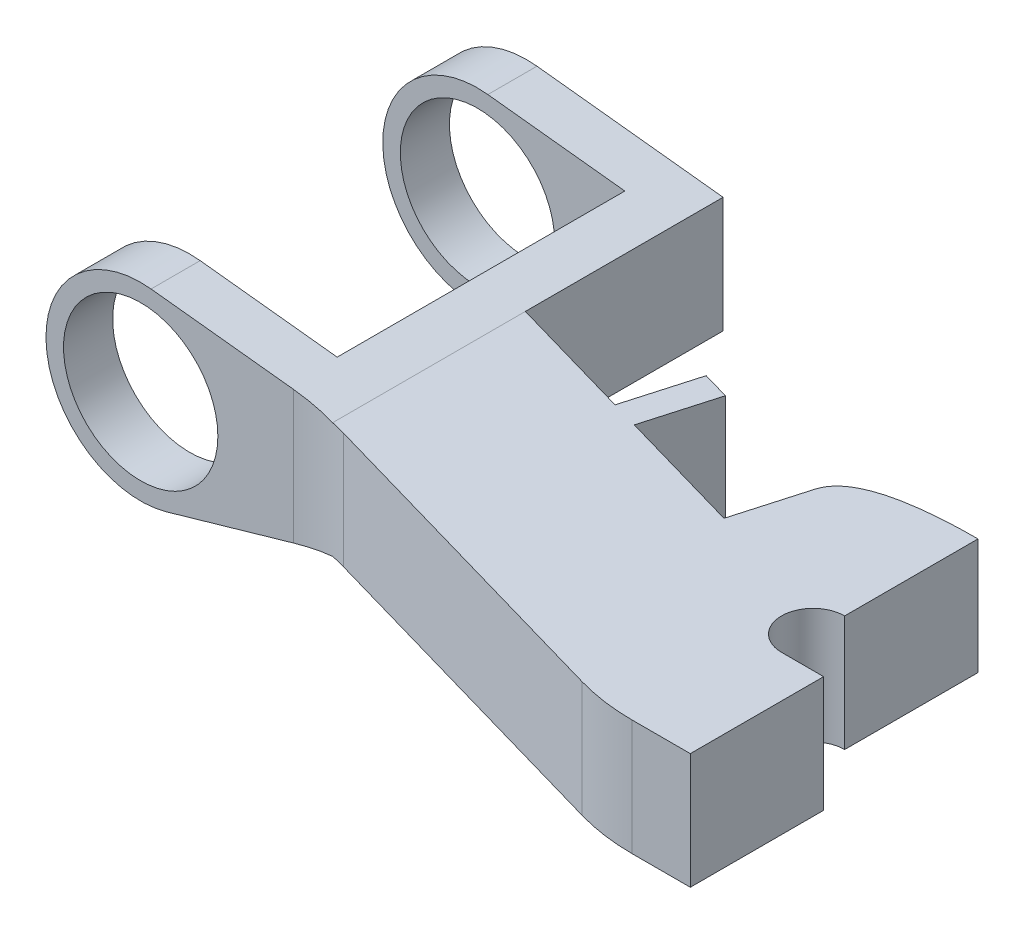
SolidWorks part; units mm, degrees
ref_plane "Спереди" through (0, 0, 0) normal (0, 0, 1) x (1, 0, 0)
ref_plane "Сверху" through (0, 0, 0) normal (0, 1, 0) x (1, 0, 0)
ref_plane "Справа" through (0, 0, 0) normal (1, 0, 0) x (0, 0, -1)
sketch "Эскиз8" plane through (0, 0, 0) normal (0, 1, 0) x (1, 0, 0)
  line L0 (-31.6673, 77.5) -> (-62.0836, 77.5) construction
  line L1 (-85, 43.6529) -> (-6, 21) construction
  line L2 (-106, 13.5) -> (-92.5, 13.5)
  line L3 (-92.5, 13.5) -> (-92.5, 6.5)
  line L4 (-92.5, 6.5) -> (-119.5, 6.5)
  line L6 (-119.5, 6.5) -> (-119.5, 13.5)
  line L7 (-119.5, 13.5) -> (-106, 13.5)
  line L8 (-117, 28.0456) -> (-95, 28.0456) construction
  line L31 (-92.5, 61.5) -> (-119.5, 61.5)
  line L32 (-119.5, 61.5) -> (-119.5, 54.5)
  line L33 (-119.5, 54.5) -> (-92.5, 54.5)
  line L34 (-92.5, 54.5) -> (-92.5, 61.5)
  line L37 (-62.0836, 77.5) -> (-62.0836, 61.5) construction
  line L38 (-62.0836, 61.5) -> (-92.5, 61.5) construction
  line L39 (-11.6673, -9.5) -> (-52.0836, -9.5) construction
  line L44 (-52.0836, -9.5) -> (-52.0836, 6.5) construction
  line L45 (-42.6378, 23.1833) -> (-38.3121, 21.943)
  line L46 (-17.6673, 16.0231) -> (-17.6673, 18.5) construction
  line L47 (-52.0836, 6.5) -> (-92.5, 6.5) construction
  line L48 (-106, 28.0456) -> (-85, 28.0456) construction
  line L52 (-92.5, 54.5) -> (-85, 54.5)
  line L53 (-85, 54.5) -> (-85, 13.5)
  line L54 (-85, 13.5) -> (-92.5, 13.5)
  line L56 (-6, 21) -> (-6, 28) construction
  line L59 (-78, 61.5) -> (-78, 63.0226)
  line L60 (-35.418, 32.0362) -> (-39.7436, 33.2766)
  line L61 (-78, 61.5) -> (-78, 33.3233)
  line L64 (-11.6673, 9.5) -> (-17.6673, 9.5)
  line L65 (-17.6673, 37.5) -> (-17.6673, 18.5) construction
  line L67 (-38.3121, 21.943) -> (-35.418, 32.0362)
  line L68 (-41.1218, 28.4703) -> (-42.6378, 23.1833) construction
  line L69 (-60.3189, 28.2533) -> (-57.4247, 38.3465) construction
  line L70 (-39.7436, 33.2766) -> (-41.1218, 28.4703)
  line L71 (-41.1218, 28.4703) -> (-36.7961, 27.2299)
  line L72 (-42.6378, 23.1833) -> (-78, 33.3233)
  line L79 (-38.3121, 21.943) -> (-17.6673, 16.0231) construction
  line L82 (-35.418, 32.0362) -> (-33.8512, 37.5) construction
  line L83 (-57.665, 38.4155) -> (-61.5101, 39.518)
  line L84 (-57.4247, 38.3465) -> (-57.665, 38.4155)
  line L85 (-57.4247, 38.3465) -> (-57.1844, 38.2776)
  line L86 (-57.1844, 38.2776) -> (-60.0786, 28.1844)
  line L87 (-61.5101, 39.518) -> (-62.8883, 34.7117)
  line L88 (-62.8883, 34.7117) -> (-58.5626, 33.4713)
  line L89 (-57.1844, 38.2776) -> (-53.3394, 37.1751)
  line L90 (-53.3394, 37.1751) -> (-56.2335, 27.0818)
  line L91 (-62.8883, 34.7117) -> (-64.4043, 29.4248) construction
  line L92 (-33.8512, 37.5) -> (-17.6673, 37.5) construction
  circle A1 centre (-106, 28.0456) radius 11
  circle A6 centre (-106, 28.0456) radius 13.5
  arc A8 (-17.6673, 18.5) -> (-17.6673, 9.5) centre (-17.6673, 14) ccw
  spline S0 degree 3 poles (-31.6673, 77.5) (-62.0836, 77.5) (-62.0836, 61.5) (-92.5, 61.5) knots 0 0 0 0 1 1 1 1
  spline S1 degree 3 poles (-11.6673, -9.5) (-52.0836, -9.5) (-52.0836, 6.5) (-92.5, 6.5) knots 0 0 0 0 1 1 1 1
  spline S3 degree 2 poles (-35.418, 32.0362) (-33.8512, 37.5) (-17.6673, 37.5) knots 0 0 0 1 1 1
  point P22 (0, 0)
  point P30 (0, 0)
  point P31 (0, 0)
  point P32 (0, 0)
  point P33 (0, 0)
  point P39 (0, 0)
  point P43 (0, 0)
  point P48 (-60.3189, 28.2533)
  point P50 (0, 0)
  point P55 (0, 0)
  point P61 (0, 0)
  point P63 (0, 0)
  point P65 (0, 0)
  point P66 (0, 0)
  point P67 (0, 0)
  point P69 (0, 0)
  point P70 (0, 0)
  point P71 (0, 0)
  point P72 (0, 0)
  point P73 (0, 0)
  point P74 (0, 0)
  point P75 (0, 0)
  point P76 (0, 0)
  point P77 (0, 0)
  point P78 (0, 0)
  point P79 (0, 0)
  point P80 (0, 0)
  point P81 (0, 0)
  point P82 (0, 0)
  point P83 (0, 0)
  point P84 (0, 0)
  point P85 (0, 0)
  point P86 (0, 0)
  point P87 (0, 0)
  point P88 (0, 0)
  point P89 (0, 0)
  point P90 (0, 0)
  point P91 (0, 0)
  point P92 (0, 0)
  point P93 (0, 0)
  point P94 (0, 0)
  point P95 (0, 0)
sketch "Эскиз10" plane through (0, 0, 0) normal (0, 1, 0) x (1, 0, 0)
  line L0 (-34.4146, 72.312) -> (-60.5171, 61.5) construction
  line L2 (-92.5, 61.5) -> (-60.5171, 61.5)
  line L3 (-52.0836, 6.5) -> (-52.0836, -1.5) construction
  line L4 (-78, 33.3233) -> (-78, 61.5)
  line L5 (-92.5, 6.5) -> (-11.6673, 6.5) construction
  line L9 (-52.0836, -1.5) -> (-11.6673, -1.5) construction
  line L11 (-52.0836, -1.5) -> (-24.1843, -9.5)
  line L13 (-92.5, 54.5) -> (-85, 54.5)
  line L14 (-85, 54.5) -> (-85, 13.5)
  line L15 (-85, 13.5) -> (-92.5, 13.5)
  line L17 (-17.6673, 9.5) -> (-11.6673, 9.5)
  line L18 (-11.6673, 9.5) -> (-11.6673, -9.5)
  line L19 (-17.6673, 18.5) -> (-17.6673, 37.5)
  line L20 (-35.418, 32.0362) -> (-33.8512, 37.5) construction
  line L21 (-52.0836, -1.5) -> (-79.9829, 6.5)
  line L22 (-33.8512, 37.5) -> (-17.6673, 37.5) construction
  line L23 (-92.5, 6.5) -> (-79.9829, 6.5)
  line L24 (-35.418, 32.0362) -> (-38.3121, 21.943)
  line L25 (-38.3121, 21.943) -> (-56.2335, 27.0818)
  line L27 (-60.0786, 28.1844) -> (-57.1844, 38.2776)
  line L28 (-57.1844, 38.2776) -> (-53.3394, 37.1751)
  line L29 (-53.3394, 37.1751) -> (-56.2335, 27.0818)
  line L30 (-60.0786, 28.1844) -> (-78, 33.3233)
  line L31 (-24.1843, -9.5) -> (-11.6673, -9.5)
  line L32 (-92.5, 61.5) -> (-119.5, 61.5)
  line L34 (-92.5, 54.5) -> (-119.5, 54.5)
  line L35 (-119.5, 61.5) -> (-119.5, 54.5)
  line L36 (-92.5, 13.5) -> (-119.5, 13.5)
  line L38 (-92.5, 6.5) -> (-119.5, 6.5)
  line L39 (-119.5, 13.5) -> (-119.5, 6.5)
  arc A1 (-17.6673, 18.5) -> (-17.6673, 9.5) centre (-17.6673, 14) ccw
  arc A2 (-17.6673, 18.5) -> (-17.6673, 9.5) centre (-17.6673, 14) ccw construction
  spline S4 degree 2 poles (-35.418, 32.0362) (-33.8512, 37.5) (-17.6673, 37.5) knots 0 0 0 1 1 1
  point P6 (0, 0)
  point P13 (0, 0)
  point P55 (0, 0)
  point P57 (0, 0)
  point P58 (0, 0)
extrude "Бобышка-Вытянуть1" add sketch "Эскиз10" along normal mid plane 27 separate body contours S4 L24 L25 L29 L28 L27 L30 L4 L2 L32 L35 L34 L13 L14 L15 L36 L39 L38 L18 L17 A1 L19 region at (-57.846, 0, -19.4318)
sketch "Эскиз11" plane through (0, 0, 0) normal (0, 0, 1) x (1, 0, 0)
  line L10 (-11.6673, -6) -> (-11.6673, 10.5)
  line L16 (-106, 0) -> (-11.6673, 0) construction
  line L31 (-11.6673, 10.5) -> (-78, 10.5)
  line L50 (-119.5, 13.5) -> (-11.6673, 13.5)
  line L51 (-119.5, 13.5) -> (-119.5, -13.5)
  line L52 (-119.5, -13.5) -> (-11.6673, -13.5)
  line L53 (-11.6673, 13.5) -> (-11.6673, -13.5)
  line L55 (-78, 10.5) -> (-78, -6)
  line L56 (-78, -6) -> (-11.6673, -6)
  line L57 (-78, -6) -> (-102.2714, -12.9749)
  line L58 (-78, 10.5) -> (-104.5232, 13.419)
  circle A2 centre (-106, 0) radius 11
  circle A5 centre (-106, 0) radius 13.5
  point P4 (0, 0)
  point P5 (0, 0)
extrude "Вырез-Вытянуть1" cut sketch "Эскиз11" against normal through all both and the other way through all contours A2 | A5 L51 L52 | A5 L50 L51 | L52 L53 | L50 L53 region at (-51.7306, -9.9565, 0) region at (-52.0379, 12.0853, 0) region at (-116.4845, -10.4845, 0) region at (-116.4845, 10.4845, 0) region at (-106, 0, 0)
sketch "Эскиз12" plane through (-62.9818, 0, -18.0597) normal (-0.9613, 0, -0.2756) x (-0.2756, 0, 0.9613)
  line L0 (-21.0327, 10.5) -> (-21.0327, -6) construction
  line L1 (-21.0327, 2.25) -> (-18.5327, 2.25) construction
  circle A0 centre (-18.5327, 2.25) radius 2.5
extrude "Бобышка-Вытянуть2" add sketch "Эскиз12" along normal blind 4.5
sketch "Эскиз13" plane through (-41.2153, 0, -11.8183) normal (-0.9613, 0, -0.2756) x (-0.2756, 0, 0.9613)
  line L0 (-21.0327, 2.25) -> (-18.5327, 2.25) construction
  line L1 (-21.0327, 10.5) -> (-21.0327, -6) construction
  circle A0 centre (-18.5327, 2.25) radius 2.5
extrude "Бобышка-Вытянуть3" add sketch "Эскиз13" along normal blind 4.5
fillet "Скругление1" radius 30 2 edges at (-24.1843, 2.25, 9.5) (-79.9829, 2.0742, -6.5)
